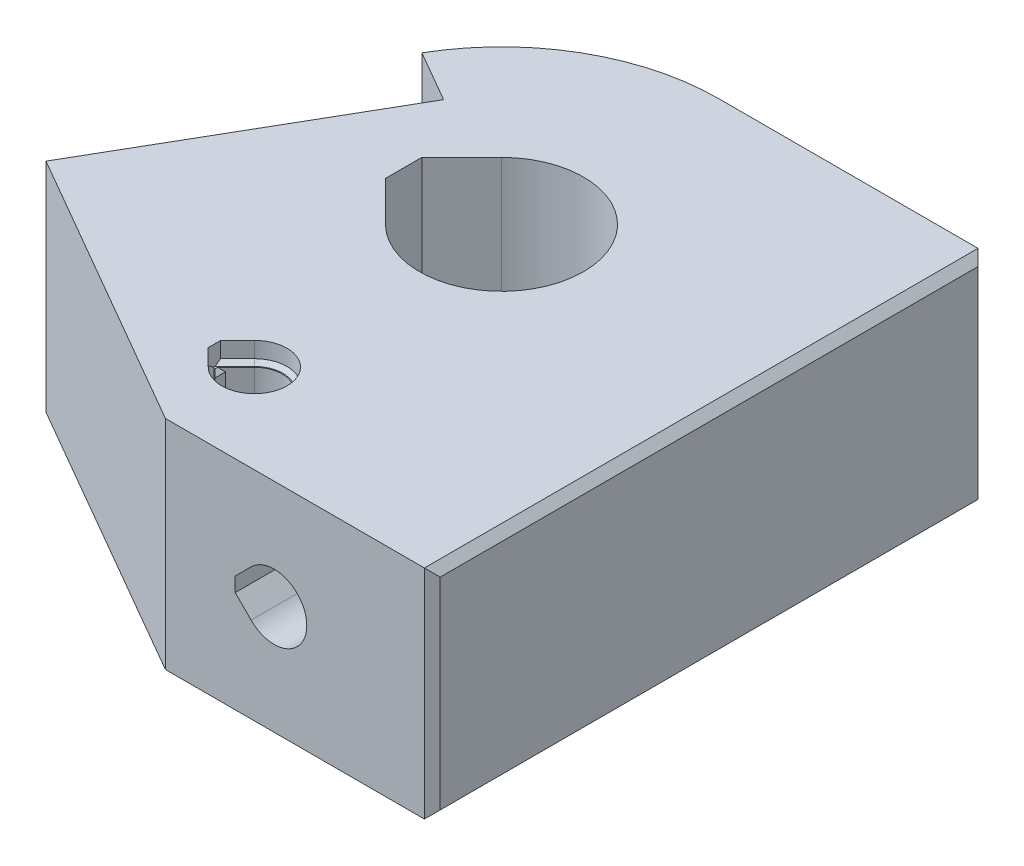
SolidWorks part; units mm, degrees
material "Custom Plastic"
ref_plane "Front Plane" through (0, 0, 0) normal (0, 0, 1) x (1, 0, 0)
ref_plane "Top Plane" through (0, 0, 0) normal (0, 1, 0) x (1, 0, 0)
ref_plane "Right Plane" through (0, 0, 0) normal (1, 0, 0) x (0, 0, -1)
sketch "Sketch1" plane through (0, 0, 0) normal (0, 1, 0) x (1, 0, 0)
  line L0 (-7.5, -1) -> (-21, -1)
  line L1 (-35.2894, 7.25) -> (-40.4856, 10.25) construction
  line L2 (-21, 24) -> (-6, 24) construction
  line L3 (0, 24) -> (0, 0) construction
  line L4 (-40.4856, 10.25) -> (-37.1244, 16.0718) construction
  line L5 (-22.7129, 20.1561) -> (-19.2871, 20.1561) construction
  line L6 (-21, 27) -> (-7.5, 27)
  line L7 (-7.5, -1) -> (-7.5, 27)
  line L8 (-35.2894, 7.25) -> (-21, -1)
  line L9 (-37.1244, 16.0718) -> (-31.9282, 13.0718) construction
  line L10 (-7.5, 11.5) -> (7.5, 20.5) construction
  line L11 (-7.5, 20.5) -> (7.5, 11.5) construction
  line L12 (-19.2871, 20.1561) -> (-18.0655, 18.9345) construction
  line L13 (-18.0655, 18.9345) -> (-21, 16) construction
  line L14 (-21, 16) -> (-23.9345, 18.9345) construction
  line L15 (-23.9345, 18.9345) -> (-22.7129, 20.1561) construction
  line L16 (-27.9282, 20) -> (-31.9282, 13.0718)
  line L17 (-27.9282, 20) -> (-30.5263, 21.5)
  line L18 (-31.9282, 13.0718) -> (-35.2894, 7.25)
  arc A0 (-21, 24) -> (-27.5362, 11.3872) centre (-21, 16) ccw construction
  circle A1 centre (-21, 16) radius 4.15
  arc A2 (-21, 27) -> (-30.5263, 21.5) centre (-21, 16) ccw
  point P10 (0, 16)
  point P22 (-21, 20.1561)
  dimension "D4" = 8.3
  dimension "D5" = 8
  dimension "D9" = 3
  dimension "D2" = 42
  dimension "D3" = 25
  dimension "D6" = 9
  dimension "D7" = 15
  dimension "D8" = 16
  dimension "D10" = 30
  dimension "D11" = 42
  dimension "D12" = 6
  dimension "D13" = 8
extrude "Boss-Extrude1" add sketch "Sketch1" along normal blind 11
sketch "Sketch2" plane through (0, 0, 1) normal (0, 0, 1) x (1, 0, 0)
  line L0 (-22.5, 21) -> (0, 21) construction
  line L1 (-15.5, 36.5) -> (15.5, 36.5) construction
  line L2 (-15.5, 36.5) -> (-15.5, 5.5) construction
  line L3 (-15.5, 5.5) -> (15.5, 5.5) construction
  line L4 (15.5, 36.5) -> (15.5, 5.5) construction
  line L5 (-15.5, 36.5) -> (15.5, 5.5) construction
  line L6 (-15.5, 5.5) -> (15.5, 36.5) construction
  line L9 (-21, 0) -> (-7.5, 0) construction
  circle A0 centre (-15.5, 36.5) radius 1.65 construction
  circle A1 centre (15.5, 36.5) radius 1.65 construction
  circle A2 centre (15.5, 5.5) radius 1.65 construction
  circle A4 centre (0, 21) radius 11.2 construction
  circle A5 centre (-15.5, 5.5) radius 1.65
  point P0 (0, 21)
  dimension "D2" = 3.3
  dimension "D3" = 22.4
  dimension "D1" = 31
  dimension "D4" = 21
extrude "Cut-Extrude1" cut sketch "Sketch2" against normal through all
sketch "Sketch3" plane through (0, 0, -27) normal (0, 0, -1) x (-1, 0, 0)
  circle A1 centre (15.5, 5.5) radius 3.7
  circle A2 centre (15.5, 5.5) radius 1.65 construction
  dimension "D1" = 7.4
extrude "Cut-Extrude2" cut sketch "Sketch3" against normal blind 11
sketch "Sketch5" plane through (0, 11, 0) normal (0, 1, 0) x (1, 0, 0)
  line L0 (0, 0) -> (0, 3.5) construction
  line L1 (-21, 3.5) -> (21, 3.5) construction
  line L3 (-21, 3.5) -> (-20.3764, 4.7535) construction
  line L4 (-20.3764, 4.7535) -> (-23.4917, 6.3032) construction
  line L5 (-21, 3.5) -> (-22.5871, 4.2896) construction
  line L6 (-22.5871, 4.2896) -> (-18.5083, 6.3032) construction
  line L7 (-18.5083, 6.3032) -> (-23.4917, 6.3032) construction
  circle A0 centre (-21, 3.5) radius 1.4
  circle A1 centre (-21, 16) radius 4.15 construction
  point P10 (-21, 6.3032)
  dimension "D1" = 2.8
  dimension "D2" = 42
  dimension "D3" = 12.5
extrude "Cut-Extrude4" cut sketch "Sketch5" against normal through all
ref_axis "Axis1" [suppressed] through (0, 6, -27) along (0, 0, 1)
ref_plane "Plane1" [suppressed] through (0, 6, 0) normal (0, 1, 0) x (1, 0, 0)
ref_axis "Axis2" through (-21, 0, -3.5) along (0, 1, 0)
ref_plane "Plane2" through (0, 5.5, 0) normal (0, 1, 0) x (1, 0, 0)
sketch "Sketch11" plane through (-29.6064, 0, -17.0933) normal (-0.866, 0, -0.5) x (-0.5, 0, 0.866)
  line L0 (15.2842, 5.5) -> (-15.2842, 5.5) construction
  line L1 (-3.3564, 11) -> (-3.3564, 0) construction
  circle A0 centre (3.6436, 5.5) radius 1.4
  dimension "D2" = 2.8
  dimension "D1" = 7
extrude "Cut-Extrude10" cut sketch "Sketch11" against normal blind 14
sketch "Sketch10" [suppressed] plane through (-29.6064, 0, -17.0933) normal (-0.866, 0, -0.5) x (-0.5, 0, 0.866)
  line L0 (0.8936, 11) -> (6.3936, 11)
  line L1 (3.6436, 2.1246) -> (6.3936, 3.7123)
  line L2 (6.3936, 3.7123) -> (6.3936, 11)
  line L3 (6.9561, 6.563) -> (3.6436, 8.4754) construction
  line L4 (3.6436, 8.4754) -> (1.4561, 7.2125) construction
  line L5 (0.8936, 11) -> (0.8936, 3.7123)
  line L6 (0.8936, 3.7123) -> (3.6436, 2.1246)
  line L7 (-3.3564, 11) -> (11.366, 11) construction
  circle A0 centre (3.6436, 5.3) radius 2.75 construction
  point P1 (3.6436, 5.5)
  dimension "D2" = 5.5
  dimension "D1" = 0.2
extrude "Cut-Extrude9" [suppressed] cut sketch "Sketch10" against normal blind 4 from offset 9 offset against normal yes
sketch "Sketch13" plane through (0, 0, -27) normal (0, 0, -1) x (-1, 0, 0)
  line L0 (15.5, 5.5) -> (18.1163, 8.1163)
  line L1 (18.1163, 8.1163) -> (19.94, 6.2926)
  line L2 (19.94, 6.2926) -> (19.94, 4.7074)
  line L3 (19.94, 4.7074) -> (18.1163, 2.8837)
  line L4 (18.1163, 2.8837) -> (15.5, 5.5)
  line L5 (15.2842, 5.5) -> (-15.2842, 5.5) construction
  circle A0 centre (15.5, 5.5) radius 3.7 construction
  arc A2 (16.85, 2.0551) -> (16.85, 8.9449) centre (15.5, 5.5) ccw construction
  point P7 (19.94, 5.5)
  point P9 (19.2, 5.5)
  dimension "D1" = 0.74
extrude "Cut-Extrude12" [suppressed] cut sketch "Sketch13" against normal up to surface (11 mm away) up to face at (-14.8375, 5.5, -16)
sketch "Sketch14" plane through (0, 0, 1) normal (0, 0, 1) x (1, 0, 0)
  line L0 (-15.5, 5.5) -> (-16.6667, 6.6667)
  line L1 (-16.6667, 6.6667) -> (-17.47, 5.8635)
  line L2 (-17.47, 5.8635) -> (-17.47, 5.1365)
  line L3 (-17.47, 5.1365) -> (-16.6667, 4.3333)
  line L4 (-16.6667, 4.3333) -> (-15.5, 5.5)
  line L5 (15.2842, 5.5) -> (-15.2842, 5.5) construction
  circle A0 centre (-15.5, 5.5) radius 1.65 construction
  point P9 (-17.15, 5.5)
  dimension "D1" = 0.32
extrude "Cut-Extrude13" [suppressed] cut sketch "Sketch14" against normal through all
sketch "Sketch16" plane through (0, 0, 0) normal (0, -1, 0) x (1, 0, 0)
  line L0 (-21, -16) -> (-23.9345, -18.9345)
  line L1 (-23.9345, -18.9345) -> (-25.95, -16.919)
  line L2 (-25.95, -16.919) -> (-25.95, -15.081)
  line L3 (-25.95, -15.081) -> (-23.9345, -13.0655)
  line L4 (-23.9345, -13.0655) -> (-21, -16)
  circle A0 centre (-21, -16) radius 4.15 construction
  point P7 (-25.15, -16)
  dimension "D1" = 0.8
extrude "Cut-Extrude14" cut sketch "Sketch16" against normal through all
chamfer "Chamfer1" [suppressed] distance 0.4 angle 45
sketch "Sketch17" plane through (0, 0, -27) normal (0, 0, -1) x (-1, 0, 0)
  line L0 (15.5, 5.5) -> (18.1163, 2.8837)
  line L1 (18.1163, 2.8837) -> (19.94, 4.7074)
  line L2 (19.94, 4.7074) -> (19.94, 6.2926)
  line L3 (19.94, 6.2926) -> (18.1163, 8.1163)
  line L4 (18.1163, 8.1163) -> (15.5, 5.5)
  line L5 (15.5, 5.5) -> (19.94, 5.5) construction
  arc A0 (16.85, 8.9449) -> (16.85, 2.0551) centre (15.5, 5.5) ccw construction
  circle A1 centre (15.5, 5.5) radius 3.7 construction
  arc A2 (16.85, 2.0551) -> (16.85, 8.9449) centre (15.5, 5.5) ccw construction
  point P6 (19.2, 5.5)
  dimension "D1" = 0.74
extrude "Cut-Extrude15" cut sketch "Sketch17" against normal up to surface (11 mm away) up to face at (-14.8375, 5.5, -16)
sketch "Sketch18" plane through (0, 0, 1) normal (0, 0, 1) x (1, 0, 0)
  line L0 (-15.5, 5.5) -> (-16.6667, 6.6667)
  line L1 (-16.6667, 6.6667) -> (-17.47, 5.8635)
  line L2 (-17.47, 5.8635) -> (-17.47, 5.1365)
  line L3 (-17.47, 5.1365) -> (-16.6667, 4.3333)
  line L4 (-16.6667, 4.3333) -> (-15.5, 5.5)
  line L5 (-15.5, 5.5) -> (-17.47, 5.5) construction
  circle A0 centre (-15.5, 5.5) radius 1.65 construction
  point P9 (-17.15, 5.5)
  dimension "D1" = 0.32
extrude "Cut-Extrude16" cut sketch "Sketch18" against normal through all
sketch "Sketch19" [suppressed] plane through (-29.6064, 0, -17.0933) normal (-0.866, 0, -0.5) x (-0.5, 0, 0.866)
  line L0 (3.6436, 5.5) -> (4.6335, 6.4899)
  line L1 (4.6335, 6.4899) -> (4.0694, 7.0541)
  line L2 (4.0694, 7.0541) -> (3.2178, 7.0541)
  line L3 (3.2178, 7.0541) -> (2.6536, 6.4899)
  line L4 (2.6536, 6.4899) -> (3.6436, 5.5)
  circle A0 centre (3.6436, 5.5) radius 1.4 construction
  circle A1 centre (3.6436, 5.5) radius 1.4 construction
  point P6 (4.3047, 6.7341)
  dimension "D1" = 0.32
extrude "Cut-Extrude17" [suppressed] cut sketch "Sketch19" against normal up to surface (14 mm away) up to face at (-20.0038, 5.5, -5.7254)
sketch "Sketch23" plane through (0, 0, 0) normal (0, -1, 0) x (1, 0, 0)
  line L0 (-21.9899, -2.5101) -> (-22.72, -3.2401)
  line L1 (-22.72, -3.2401) -> (-22.72, -3.7599)
  line L2 (-22.72, -3.7599) -> (-21.9899, -4.4899)
  line L3 (-21.9899, -4.4899) -> (-21.9899, -2.5101)
  line L4 (-21, -3.5) -> (-22.72, -3.5) construction
  circle A0 centre (-21, -3.5) radius 1.4 construction
  point P9 (-22.4, -3.5)
  dimension "D1" = 0.32
extrude "Cut-Extrude21" cut sketch "Sketch23" against normal through all
sketch "Sketch20" plane through (0, 11, 0) normal (0, 1, 0) x (1, 0, 0)
  circle A0 centre (-21, 3.5) radius 1.65
  dimension "D1" = 3.3
extrude "Cut-Extrude18" cut sketch "Sketch20" against normal blind 1
sketch "Sketch21" plane through (0, 0, 0) normal (0, -1, 0) x (1, 0, 0)
  circle A0 centre (-21, -3.5) radius 1.65
  circle A1 centre (-21, -3.5) radius 1.65 construction
extrude "Cut-Extrude19" cut sketch "Sketch21" against normal blind 1
sketch "Sketch24" plane through (0, 0, 0) normal (0, -1, 0) x (1, 0, 0)
  line L0 (-22.1667, -2.3333) -> (-23.02, -3.1865)
  line L1 (-23.02, -3.1865) -> (-23.02, -3.8135)
  line L2 (-23.02, -3.8135) -> (-22.1667, -4.6667)
  line L3 (-22.1667, -4.6667) -> (-22.1667, -2.3333)
  line L4 (-22.6074, -3.1275) -> (-21.9899, -2.5101) construction
  line L5 (-22.72, -3.2401) -> (-22.72, -3.7599) construction
  arc A0 (-22.6074, -3.8725) -> (-22.6074, -3.1275) centre (-21, -3.5) ccw construction
  dimension "D1" = 0.3
extrude "Cut-Extrude22" cut sketch "Sketch24" against normal up to surface (1 mm away) up to face at (-20.8868, 1, -3.5)
sketch "Sketch25" plane through (0, 11, 0) normal (0, 1, 0) x (1, 0, 0)
  line L0 (-23.02, 3.1865) -> (-23.02, 3.8135)
  line L1 (-23.02, 3.8135) -> (-22.1667, 4.6667)
  line L2 (-22.1667, 4.6667) -> (-22.1667, 2.3333)
  line L3 (-22.1667, 2.3333) -> (-23.02, 3.1865)
  arc A0 (-22.6074, 3.1275) -> (-22.6074, 3.8725) centre (-21, 3.5) ccw construction
extrude "Cut-Extrude23" cut sketch "Sketch25" against normal up to surface (1 mm away) up to face at (-20.8868, 10, -3.5)
fillet "Fillet1" [suppressed] radius 3
chamfer "Chamfer4" distance 0.4 angle 45 4 edges at (-7.5, 5.5, 1) (-7.5, 11, -13) (-7.5, 5.5, -27) (-7.5, 0, -13)
sketch "Sketch22" plane through (-29.6064, 0, -17.0933) normal (-0.866, 0, -0.5) x (-0.5, 0, 0.866)
  line L0 (2.4415, 6.7021) -> (3.2694, 7.53) construction
  line L1 (3.2694, 7.53) -> (4.0178, 7.53) construction
  line L2 (4.0178, 7.53) -> (4.8457, 6.7021) construction
  arc A0 (2.4415, 6.7021) -> (4.8457, 6.7021) centre (3.6436, 5.5) ccw
  circle A1 centre (3.6436, 5.5) radius 1.4 construction
  arc A2 (4.8457, 6.7021) -> (2.4415, 6.7021) centre (3.6436, 5.5) ccw
  point P1 (3.6436, 7.2)
  dimension "D1" = 1.7
  dimension "D2" = 0.33
extrude "Cut-Extrude20" cut sketch "Sketch22" against normal blind 9
chamfer "Chamfer3" [suppressed] distance 0.6 angle 15
chamfer "Chamfer2" [suppressed] distance 0.4 angle 45
chamfer "Chamfer5" distance 0.2 angle 45 8 edges at (-22.355, 1, -4.1249) (-19.6, 1, -3.5) (-22.355, 1, -2.8751) (-22.72, 1, -3.5) (-22.72, 10, -3.5) (-22.5934, 10, -2.7599) (-22.5934, 10, -4.2401) (-19.35, 10, -3.5)
sketch "Sketch26" plane through (-5.683, 0, 9.8433) normal (-0.5, 0, 0.866) x (0.866, 0, 0.5)
  line L0 (-34.1865, 0) -> (-34.1865, 2)
  line L2 (-34.1865, 2) -> (-37.6865, 2)
  line L3 (-34.1865, 11) -> (-34.1865, 0) construction
  line L4 (-37.6865, 2) -> (-37.6865, 0)
  line L5 (-37.6865, 0) -> (-34.1865, 0)
  line L6 (-34.1865, 0) -> (-17.6865, 0) construction
  line L7 (-37.6865, 11) -> (-34.1865, 11)
  line L8 (-37.6865, 11) -> (-37.6865, 9)
  line L9 (-37.6865, 9) -> (-34.1865, 9)
  line L10 (-34.1865, 11) -> (-34.1865, 9)
  dimension "D1" = 2
  dimension "D2" = 3.5
extrude "Cut-Extrude24" [suppressed] cut sketch "Sketch26" against normal up to next
chamfer "Chamfer6" [suppressed] distance 3 angle 10
chamfer "Chamfer7" [suppressed] distance 2 angle 45
chamfer "Chamfer9" [suppressed] distance 1 angle 8
sketch "Sketch27" [suppressed] plane through (0, 5.5, 0) normal (0, 1, 0) x (1, 0, 0)
  line L0 (-38.5803, 9.15) -> (-38.5803, 13.55)
  line L1 (-38.1244, 14.3397) -> (-39.4856, 11.9821) construction
  line L2 (-38.5803, 13.55) -> (-40.4856, 10.25)
  line L3 (-40.4856, 10.25) -> (-38.5803, 9.15)
  line L4 (-21, -1) -> (-35.2894, 7.25) construction
  line L5 (-37.8205, 9.866) -> (-38.3205, 9) construction
  dimension "D1" = 0.3
extrude "Cut-Extrude25" [suppressed] cut sketch "Sketch27" against normal through all and the other way through all
fillet "Fillet2" [suppressed] radius 1
